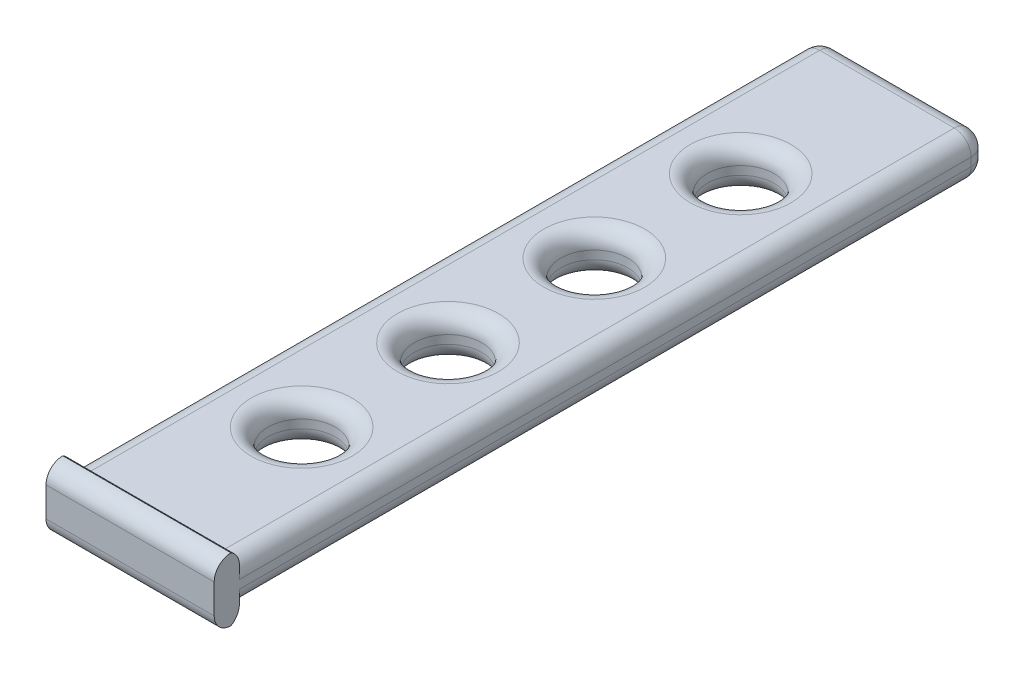
SolidWorks part; units mm, degrees
ref_plane "Front Plane" through (0, 0, 0) normal (0, 0, 1) x (1, 0, 0)
ref_plane "Top Plane" through (0, 0, 0) normal (0, 1, 0) x (1, 0, 0)
ref_plane "Right Plane" through (0, 0, 0) normal (1, 0, 0) x (0, 0, -1)
sketch "Sketch1" plane through (0, 0, 0) normal (0, 1, 0) x (1, 0, 0)
  line L0 (-12.7, 0) -> (12.7, 0)
  line L1 (-12.7, 67.3207) -> (-12.7, 0)
  line L2 (12.7, 67.3207) -> (12.7, 0)
  line L3 (-12.7, 67.3207) -> (-12.7, 113.0407)
  line L4 (-12.7, 113.0407) -> (12.7, 113.0407)
  line L5 (12.7, 113.0407) -> (12.7, 67.3207)
  point P4 (0, 0)
  dimension "D1" = 67.3207
  dimension "D3" = 45.72
  dimension "D4" = 25.4
extrude "Boss-Extrude1" add sketch "Sketch1" along normal blind 6.35 contours L3 L4 L5 L2 L0 L1
sketch "Sketch3" plane through (0, 0, 0) normal (0, 0, 1) x (1, 0, 0)
  line L1 (-12.7, 7.9375) -> (12.7, 7.9375)
  line L2 (-12.7, 7.9375) -> (-12.7, -1.5875)
  line L3 (-12.7, -1.5875) -> (12.7, -1.5875)
  line L4 (12.7, 7.9375) -> (12.7, -1.5875)
  line L5 (-12.7, 6.35) -> (-12.7, 0) construction
  line L7 (12.7, 6.35) -> (12.7, 0) construction
  dimension "D1" = 9.525
  dimension "D2" = 1.5875
extrude "Boss-Extrude3" add sketch "Sketch3" along normal blind 3.81 contours L1 L4 L3 L2
fillet "Fillet1" radius 2.54 1 edges at (0, 7.9375, 3.81)
fillet "Fillet2" radius 2.54 1 edges at (0, -1.5875, 3.81)
fillet "Fillet5" radius 2.54 4 edges at (-12.7, 6.35, -56.5204) (-12.7, 0, -56.5204) (12.7, 0, -56.5204) (12.7, 6.35, -56.5204)
fillet "Fillet6" radius 2.54 8 edges at (-11.9561, 5.6061, -113.0407) (-12.7, 3.175, -113.0407) (11.9561, 0.7439, -113.0407) (12.7, 3.175, -113.0407) (11.9561, 5.6061, -113.0407) (0, 0, -113.0407) (-11.9561, 0.7439, -113.0407) (0, 6.35, -113.0407)
fillet "Fillet7" radius 2.54 1 edges at (0, -1.5875, 0)
fillet "Fillet8" radius 2.54 1 edges at (0, 7.9375, 0)
sketch "Sketch4" plane through (0, 0, 0) normal (0, -1, 0) x (1, 0, 0)
  line L0 (0, 0) -> (0, -22.1001) construction
  line L1 (0, -22.1001) -> (0, -44.2003) construction
  line L2 (0, -44.2003) -> (0, -66.3004) construction
  line L3 (0, -66.3004) -> (0, -88.4006) construction
  line L4 (0, -88.4006) -> (0, -110.5007) construction
  line L5 (-10.16, -110.5007) -> (10.16, -110.5007) construction
  circle A0 centre (0, -22.1001) radius 5.08
  circle A1 centre (0, -44.2003) radius 5.08
  circle A2 centre (0, -66.3004) radius 5.08
  circle A3 centre (0, -88.4006) radius 5.08
  dimension "D1" = 10.16
extrude "Cut-Extrude1" cut sketch "Sketch4" against normal through all
fillet "Fillet11" radius 2.54 4 edges at (0, 6.35, -17.0201) (0, 6.35, -39.1203) (0, 6.35, -61.2204) (0, 6.35, -83.3206)
fillet "Fillet12" radius 2.54 4 edges at (0, 0, -27.1801) (0, 0, -49.2803) (0, 0, -71.3804) (0, 0, -93.4806)
